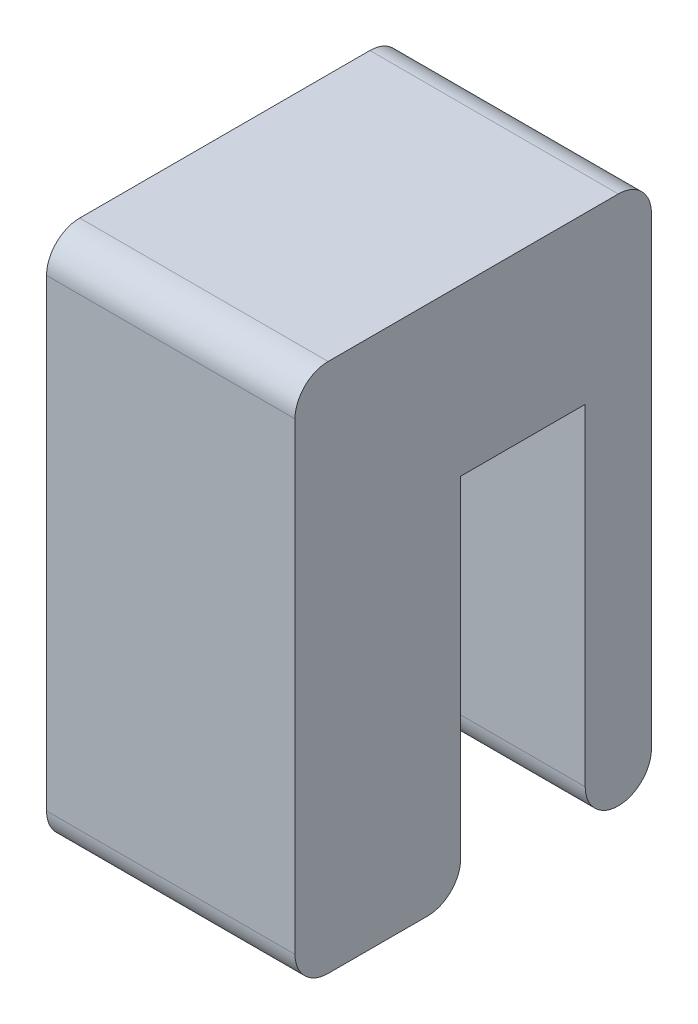
SolidWorks part; units mm, degrees
ref_plane "Front Plane" through (0, 0, 0) normal (0, 0, 1) x (1, 0, 0)
ref_plane "Top Plane" through (0, 0, 0) normal (0, 1, 0) x (1, 0, 0)
ref_plane "Right Plane" through (0, 0, 0) normal (1, 0, 0) x (0, 0, -1)
sketch "Sketch1" plane through (0, 0, 0) normal (1, 0, 0) x (0, 0, -1)
  line L0 (0, -27.94) -> (0, 0)
  line L1 (0, 0) -> (9.5504, 0)
  line L2 (9.5504, 0) -> (9.5504, -27.94)
  line L9 (14.6304, 12.7) -> (-12.7, 12.7)
  line L10 (-12.7, 12.7) -> (-12.7, -27.94)
  line L11 (-12.7, -27.94) -> (0, -27.94)
  line L12 (14.6304, 12.7) -> (14.6304, -27.94)
  line L13 (14.6304, -27.94) -> (9.5504, -27.94)
  point P2 (-6.35, -27.94)
  dimension "D1" = 12.7
  dimension "D2" = 12.7
  dimension "D3" = 5.08
  dimension "D4" = 27.94
  dimension "D5" = 9.5504
  dimension "D6" = 0
extrude "Boss-Extrude1" add sketch "Sketch1" along normal blind 19.05
fillet "Fillet3" radius 2.54 6 edges at (9.525, 12.7, -14.6304) (9.525, -27.94, -14.6304) (9.525, -27.94, -9.5504) (9.525, -27.94, 0) (9.525, -27.94, 12.7) (9.525, 12.7, 12.7)
